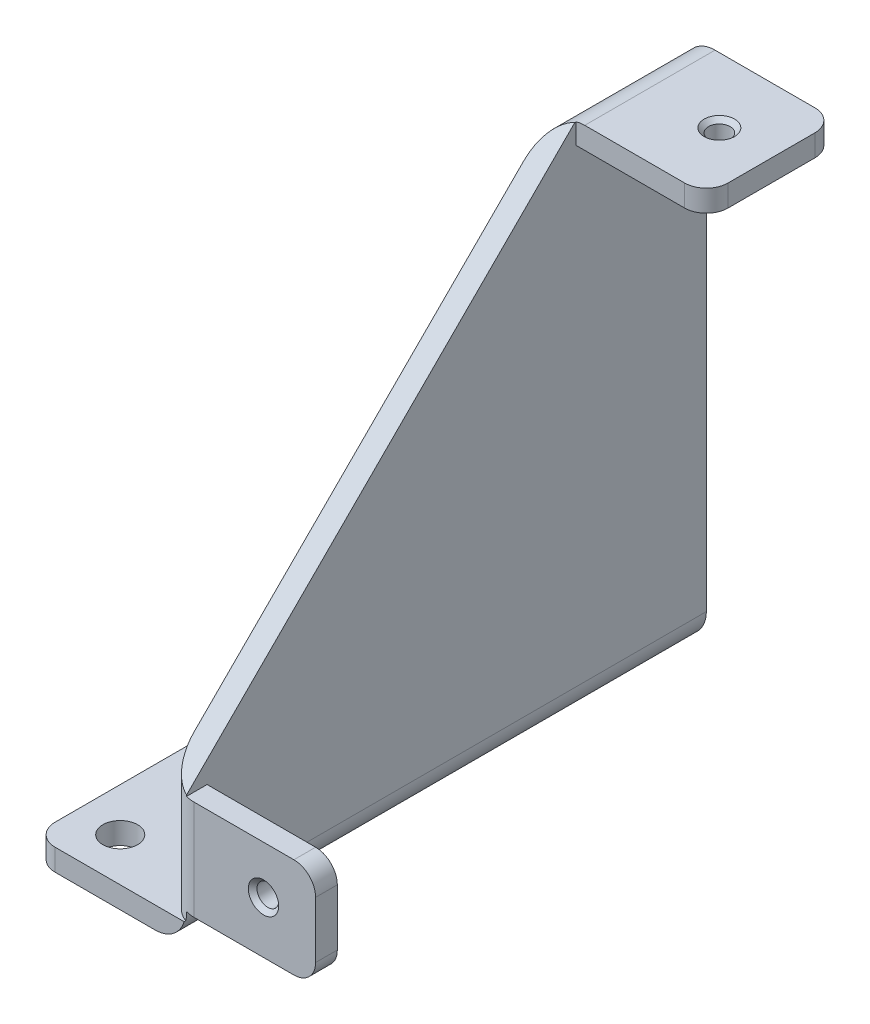
SolidWorks part; units mm, degrees
material "Acciaio al carbonio semplice"
ref_plane "Piano frontale" through (0, 0, 0) normal (0, 0, 1) x (1, 0, 0)
ref_plane "Piano superiore" through (0, 0, 0) normal (0, 1, 0) x (1, 0, 0)
ref_plane "Piano destro" through (0, 0, 0) normal (1, 0, 0) x (0, 0, -1)
sketch "Schizzo1" plane through (0, 0, 0) normal (1, 0, 0) x (0, 0, -1)
  line L0 (0, 0) -> (0, 120)
  line L1 (0, 120) -> (-30, 120)
  line L2 (-30, 120) -> (-120, 30)
  line L3 (-120, 30) -> (-120, 0)
  line L4 (-120, 0) -> (0, 0)
  dimension "D1" = 120
  dimension "D2" = 30
extrude "Estrusione-Estrusione1" add sketch "Schizzo1" along normal blind 5
sketch "Schizzo2" plane through (0, 0, 0) normal (-1, 0, 0) x (0, 0, 1)
  line L0 (120, 30) -> (120, 0) construction
  line L1 (0, 0) -> (120, 0)
  line L2 (0, 0) -> (0, 5)
  line L3 (0, 5) -> (120, 5)
  line L4 (120, 0) -> (120, 5)
  dimension "D1" = 5
extrude "Estrusione-Estrusione2" add sketch "Schizzo2" along normal blind 30
fillet "Raccordo1" radius 7 1 edges at (5, 0, 60)
sketch "Schizzo3" plane through (5, 0, 0) normal (1, 0, 0) x (0, 0, -1)
  line L0 (-120, 7) -> (0, 7) construction
  line L1 (-120, 30) -> (-115, 30)
  line L2 (-120, 30) -> (-120, 7)
  line L3 (-120, 7) -> (-115, 7)
  line L4 (-115, 30) -> (-115, 7)
  line L6 (0, 120) -> (-30, 120)
  line L7 (0, 120) -> (0, 115)
  line L8 (0, 115) -> (-30, 115)
  line L9 (-30, 120) -> (-30, 115)
  dimension "D1" = 5
  dimension "D2" = 5
extrude "Estrusione-Estrusione3" add sketch "Schizzo3" along normal blind 30
fillet "Raccordo3" radius 7 2 edges at (0, 120, 15)
hole_wizard "Foro filettato M6-1" positions "Schizzo5" profile "Schizzo4" tap size "M6" standard "ISO"
sketch "Schizzo5" plane through (0, 120, 0) normal (0, 1, 0) x (-1, 0, 0)
  line L0 (-35, 0) -> (-7, 0) construction
  line L1 (-35, 0) -> (-35, 30) construction
  point P0 (-23, 15)
  dimension "D1" = 15
  dimension "D2" = 12
sketch "Schizzo4" plane through (23, 120, 15) normal (1, 0, 0) x (0, 0, 1)
  line L0 (0, 0) -> (0, 12.5022)
  line L1 (0, 12.5022) -> (2.5, 11)
  line L2 (2.5, 11) -> (2.5, 1)
  line L3 (2.5, 1) -> (3.5, 0)
  line L5 (3.5, 0) -> (0, 0)
  line L6 (-2.5, 1) -> (-3.5, 0) construction
  line L10 (0, 12.5022) -> (-2.5, 11) construction
  line L11 (0, -6.35) -> (0, 107.95) construction
  dimension "Tap Drill Dia." = 5
  dimension "Tap Drill Depth" = 11
  dimension "Near C'Sink Dia." = 7
  dimension "Near C'Sink Angle" = 90
  dimension "Drill Angle" = 118
cosmetic thread "Filettatura del foro1" parameters "D1"=5, "D2"=6
hole_wizard "Foro filettato M6-2" positions "Schizzo7" profile "Schizzo6" tap size "M6" standard "ISO"
sketch "Schizzo7" plane through (0, 0, 120) normal (0, 0, 1) x (1, 0, 0)
  line L0 (35, 30) -> (35, 7) construction
  line L1 (35, 30) -> (7, 30) construction
  point P0 (23, 19)
  dimension "D1" = 12
  dimension "D2" = 11
sketch "Schizzo6" plane through (23, 19, 120) normal (1, 0, 0) x (0, -1, 0)
  line L0 (0, 0) -> (0, 12.5022)
  line L1 (0, 12.5022) -> (2.5, 11)
  line L2 (2.5, 11) -> (2.5, 1)
  line L3 (2.5, 1) -> (3.5, 0)
  line L5 (3.5, 0) -> (0, 0)
  line L6 (-2.5, 1) -> (-3.5, 0) construction
  line L10 (0, 12.5022) -> (-2.5, 11) construction
  line L11 (0, -6.35) -> (0, 107.95) construction
  dimension "Tap Drill Dia." = 5
  dimension "Tap Drill Depth" = 11
  dimension "Near C'Sink Dia." = 7
  dimension "Near C'Sink Angle" = 90
  dimension "Drill Angle" = 118
cosmetic thread "Filettatura del foro2" parameters "D1"=5, "D2"=6
fillet "Raccordo2" radius 5 6 edges at (-30, 2.5, 0) (-30, 2.5, 120) (35, 117.5, 0) (35, 117.5, 30) (35, 30, 117.5) (35, 7, 117.5)
sketch "Schizzo8" plane through (0, 5, 0) normal (0, 1, 0) x (1, 0, 0)
  line L0 (-25, -120) -> (4.7082, -120) construction
  line L1 (-30, -115) -> (-30, -5) construction
  circle A0 centre (-20, -10) radius 4
  circle A1 centre (-20, -110) radius 4
  dimension "D1" = 100
  dimension "D2" = 10
  dimension "D3" = 10
  dimension "D4" = 8
extrude "Taglio-Estrusione1" cut sketch "Schizzo8" against normal through all
